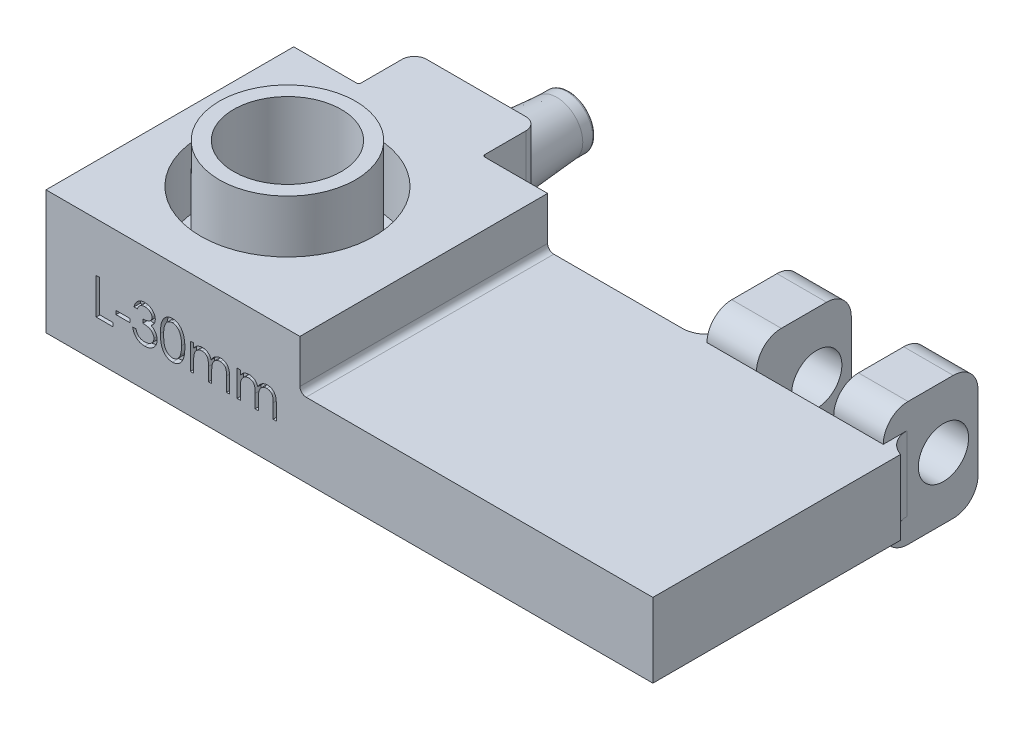
SolidWorks part; units mm, degrees
ref_plane "Front Plane" through (0, 0, 0) normal (0, 0, 1) x (1, 0, 0)
ref_plane "Top Plane" through (0, 0, 0) normal (0, 1, 0) x (1, 0, 0)
ref_plane "Right Plane" through (0, 0, 0) normal (1, 0, 0) x (0, 0, -1)
sketch "Sketch2" plane through (0, 0, 0) normal (0, 1, 0) x (1, 0, 0)
  line L1 (-14.4231, 13.5577) -> (34.5769, 13.5577)
  line L2 (-14.4231, 13.5577) -> (-14.4231, -6.4423)
  line L3 (-14.4231, -6.4423) -> (34.5769, -6.4423)
  line L4 (34.5769, 13.5577) -> (34.5769, -6.4423)
  dimension "D1" = 49
  dimension "D2" = 20
extrude "Boss-Extrude1" add sketch "Sketch2" along normal blind 10
sketch "Sketch3" plane through (0, 0, 0) normal (0, -1, 0) x (1, 0, 0)
  line L0 (34.5769, 6.4423) -> (34.5769, -13.5577) construction
  line L1 (27.5769, -5.0677) -> (-2.4231, -5.0677)
  line L2 (27.5769, -5.0677) -> (27.5769, -2.0477)
  line L3 (27.5769, -2.0477) -> (-2.4231, -2.0477)
  line L4 (-2.4231, -5.0677) -> (-2.4231, -2.0477)
  line L5 (-14.4231, -3.5577) -> (34.5769, -3.5577) construction
  line L6 (-14.4231, -13.5577) -> (-14.4231, 6.4423) construction
  dimension "D1" = 30
  dimension "D2" = 7
  dimension "D3" = 3.02
  dimension "D4" = 1.51
extrude "Cut-Extrude1" cut sketch "Sketch3" against normal blind 2
sketch "Sketch4" plane through (0, 0, 0) normal (0, -1, 0) x (1, 0, 0)
  line L0 (-2.4231, -2.0477) -> (-2.4231, -5.0677) construction
  line L1 (-2.4231, -6.0477) -> (-7.4231, -6.0477)
  line L2 (-2.4231, -6.0477) -> (-2.4231, -1.0477)
  line L3 (-2.4231, -1.0477) -> (-7.4231, -1.0477)
  line L4 (-7.4231, -6.0477) -> (-7.4231, -1.0477)
  line L6 (27.5769, -2.0477) -> (-2.4231, -2.0477) construction
  dimension "D1" = 5
  dimension "D2" = 5
  dimension "D3" = 1
extrude "Cut-Extrude2" cut sketch "Sketch4" against normal blind 5
sketch "Sketch5" plane through (0, 5, 0) normal (0, -1, 0) x (1, 0, 0)
  line L0 (-7.4231, -3.5477) -> (-2.4231, -3.5577) construction
  line L1 (-7.4231, -1.0477) -> (-7.4231, -6.0477) construction
  line L2 (-2.4231, -2.0477) -> (-2.4231, -5.0677) construction
  circle A0 centre (-4.9231, -3.5527) radius 7
  dimension "D1" = 14
extrude "Cut-Extrude3" cut sketch "Sketch5" against normal through all
sketch "Sketch6" plane through (0, 5, 0) normal (0, 1, 0) x (1, 0, 0)
  line L0 (-4.0731, 1.0477) -> (-2.4231, 1.0477)
  line L1 (-7.4231, 6.0477) -> (-5.7731, 6.0477)
  line L2 (-7.4231, 6.0477) -> (-7.4231, 1.0477)
  line L3 (-7.4231, 1.0477) -> (-5.7731, 1.0477)
  line L4 (-2.4231, 6.0477) -> (-2.4231, 1.0477)
  line L5 (-4.0731, 6.0477) -> (-2.4231, 6.0477)
  line L7 (-5.7731, 6.0477) -> (-5.7731, 1.0477)
  line L9 (-4.0731, 6.0477) -> (-4.0731, 1.0477)
  dimension "D1" = 1.7
extrude "Boss-Extrude2" add sketch "Sketch6" against normal blind 0.5
sketch "Sketch11" plane through (0, 0, 0) normal (0, -1, 0) x (1, 0, 0)
  circle A0 centre (28.8884, -3.5577) radius 2
  dimension "D1" = 4
extrude "Cut-Extrude4" cut sketch "Sketch11" against normal up to surface (2 mm away) up to face at (12.5769, 2, -3.5577)
sketch "Sketch12" plane through (0, 0, 0) normal (0, -1, 0) x (1, 0, 0)
  line L1 (-7.4231, -1.0477) -> (-2.4231, -1.0477)
  line L2 (-7.4231, -1.0477) -> (-7.4231, -6.0477)
  line L3 (-7.4231, -6.0477) -> (-2.4231, -6.0477)
  line L4 (-2.4231, -1.0477) -> (-2.4231, -6.0477)
extrude "Boss-Extrude4" add sketch "Sketch12" against normal blind 0.8
sketch "Sketch14" plane through (0, 0, 6.4423) normal (0, 0, 1) x (1, 0, 0)
  line L0 (-14.4231, 10) -> (34.5769, 10) construction
  line L1 (6.0769, 10) -> (34.5769, 10)
  line L2 (6.0769, 10) -> (6.0769, 6)
  line L3 (6.0769, 6) -> (34.5769, 6)
  line L4 (34.5769, 10) -> (34.5769, 6)
  line L5 (34.5769, 10) -> (34.5769, 0) construction
  line L6 (27.5769, 2) -> (-2.4231, 2) construction
  line L7 (2.0769, 5) -> (2.0769, 10) construction
  dimension "D1" = 4
  dimension "D2" = 4
extrude "Cut-Extrude6" cut sketch "Sketch14" against normal through all
fillet "Fillet1" radius 0.5 1 edges at (6.0769, 6, -3.5577)
sketch "Sketch13" plane through (0, 0, 6.4423) normal (0, 0, 1) x (1, 0, 0)
  line L0 (-10.748, 3.1258) -> (12.5164, 3.1258) construction
  text T0 "L-30mm" font "Century Gothic" height in points 11
extrude "Cut-Extrude5" cut sketch "Sketch13" against normal blind 0.5
sketch "Sketch19" plane through (0, 10, 0) normal (0, 1, 0) x (1, 0, 0)
  line L0 (6.0769, 13.5577) -> (-14.4231, 13.5577) construction
  line L1 (-9.1731, 18.0477) -> (0.8269, 18.0477)
  line L2 (-9.1731, 18.0477) -> (-9.1731, 13.5577)
  line L3 (-9.1731, 13.5577) -> (0.8269, 13.5577)
  line L4 (0.8269, 18.0477) -> (0.8269, 13.5577)
  line L6 (-4.1731, -6.4423) -> (-4.1731, 18.0477) construction
  line L8 (-14.4231, -6.4423) -> (6.0769, -6.4423) construction
  dimension "D1" = 10
  dimension "D3" = 12
extrude "Boss-Extrude5" add sketch "Sketch19" against normal up to surface (10 mm away) up to face at (13.4048, 0, -3.5577)
fillet "Fillet2" radius 1 2 edges at (-9.1731, 5, -18.0477) (0.8269, 5, -18.0477)
sketch "Sketch20" plane through (0, 0, -18.0477) normal (0, 0, -1) x (-1, 0, 0)
  line L0 (8.1731, 0) -> (0.1731, 0) construction
  circle A0 centre (4.6731, 3.5) radius 0.5
  dimension "D1" = 1
  dimension "D2" = 3.5
extrude "Cut-Extrude7" cut sketch "Sketch20" against normal up to next
sketch "Sketch21" plane through (0, 0, -18.0477) normal (0, 0, -1) x (-1, 0, 0)
  circle A0 centre (4.6731, 3.5) radius 1.4
  dimension "D1" = 2.8
extrude "Cut-Extrude8" cut sketch "Sketch21" against normal offset from surface (10 mm away) 2 up to face at (-5.1731, 3.5, -6.0477)
ref_axis "Axis1" through (-4.6731, 3.5, -8.0477) along (0, 0, -1)
ref_plane "Plane1" through (0, 3.5, 0) normal (0, -1, 0) x (-1, 0, 0)
sketch "Sketch23" plane through (0, 3.5, 0) normal (0, -1, 0) x (-1, 0, 0)
  line L0 (4.6731, 15.6131) -> (4.6731, 26.4829) construction
  line L1 (4.6731, 8.0477) -> (4.6731, 18.0477) construction
  line L2 (6.2731, 26.0477) -> (6.7731, 26.0477)
  line L3 (6.7731, 26.0477) -> (6.7731, 25.0477)
  line L4 (6.7731, 25.0477) -> (7.1731, 20.1558)
  line L5 (7.0734, 20.0477) -> (6.7731, 20.0477)
  line L6 (6.7731, 20.0477) -> (6.7731, 18.0477)
  line L7 (8.1731, 18.0477) -> (0.1731, 18.0477) construction
  line L8 (6.7731, 18.0477) -> (6.2731, 18.0477)
  line L9 (6.2731, 18.0477) -> (6.2731, 26.0477)
  arc A0 (7.0734, 20.0477) -> (7.1731, 20.1558) centre (7.0734, 20.1477) ccw
  dimension "D1" = 0.1
  dimension "D2" = 0.5
  dimension "D3" = 4.2
  dimension "D4" = 5
  dimension "D5" = 8
  dimension "D6" = 7
  dimension "D7" = 5
revolve "Revolve1" add sketch "Sketch23" angle 360 about L0
fillet "Fillet3" radius 0.2 5 edges at (-3.0731, 3.5, -26.0477) (-2.5731, 3.5, -26.0477) (-6.7731, 3.5, -18.0477)
sketch "Sketch24" plane through (0, 5, 0) normal (0, 1, 0) x (1, 0, 0)
  line L5 (-5.7731, 1.0477) -> (-5.7731, 6.0477) construction
  line L6 (-4.0731, 1.0477) -> (-5.7731, 1.0477)
  line L7 (-4.0731, 1.0477) -> (-4.0731, 4.0477)
  line L8 (-4.0731, 4.0477) -> (-5.7731, 4.0477)
  line L9 (-5.7731, 1.0477) -> (-5.7731, 4.0477)
  dimension "D1" = 3
extrude "Boss-Extrude6" add sketch "Sketch24" against normal up to vertex (0.5 mm away) up to point (-5.7731, 4.5, -1.0477)
sketch "Sketch29" plane through (0, 6, 0) normal (0, 1, 0) x (1, 0, 0)
  line L0 (29.0269, 13.5577) -> (29.0269, -8.2906) construction
  line L1 (34.5769, 13.5577) -> (34.5769, -6.4423) construction
  line L2 (23.0969, 13.5577) -> (23.0969, -8.2906) construction
  line L3 (34.5769, 13.5577) -> (1.0269, 13.5577) construction
  point P6 (0, 0)
  point P9 (0, 0)
  point P10 (0, 0)
  dimension "D1" = 5.55
  dimension "D2" = 5.93
sketch "Sketch34" plane through (0, 5, 0) normal (0, 1, 0) x (1, 0, 0)
  circle A0 centre (-4.9231, 3.5527) radius 4.35
  circle A1 centre (-4.9231, 3.5527) radius 5.5
  dimension "D1" = 8.7
  dimension "D2" = 11
extrude "Boss-Extrude10" add sketch "Sketch34" along normal blind 8.2
sketch "Sketch36" plane through (0, 0, -13.5577) normal (0, 0, -1) x (-1, 0, 0)
  line L0 (-6.5769, 6) -> (-34.5769, 6) construction
  line L1 (-34.5769, 3) -> (-17, 3) construction
  line L2 (-34.5769, 6) -> (-34.5769, 0) construction
  line L4 (-33.1769, -2) -> (-29.1769, -2)
  line L5 (-33.1769, -2) -> (-33.1769, 8)
  line L6 (-33.1769, 8) -> (-29.1769, 8)
  line L7 (-29.1769, -2) -> (-29.1769, 8)
  line L8 (-33.1769, -2) -> (-29.1769, 8) construction
  line L9 (-33.1769, 8) -> (-29.1769, -2) construction
  line L10 (-22.9469, -2) -> (-18.9469, -2)
  line L11 (-22.9469, -2) -> (-22.9469, 8)
  line L12 (-22.9469, 8) -> (-18.9469, 8)
  line L13 (-18.9469, -2) -> (-18.9469, 8)
  line L14 (-22.9469, -2) -> (-18.9469, 8) construction
  line L15 (-22.9469, 8) -> (-18.9469, -2) construction
  point P0 (-29.0269, 6)
  point P1 (-31.1769, 3)
  point P5 (-23.0969, 6)
  point P15 (-20.9469, 3)
  dimension "D1" = 10
  dimension "D2" = 4
  dimension "D3" = 0.15
  dimension "D4" = 0.15
extrude "Boss-Extrude11" add sketch "Sketch36" along normal blind 7.65
sketch "Sketch37" plane through (33.1769, 0, 0) normal (1, 0, 0) x (0, 0, -1)
  line L0 (21.2077, 8) -> (21.2077, -2) construction
  line L1 (13.5577, 6) -> (13.5577, 0) construction
  circle A0 centre (18.4177, 3) radius 2.03
  point P4 (0, 0)
  point P7 (13.5577, 3)
  dimension "D1" = 4.06
  dimension "D2" = 2.79
extrude "Cut-Extrude9" cut sketch "Sketch37" against normal up to surface (14.23 mm away) up to face at (18.9469, 3, -16.1077)
fillet "Fillet4" radius 2 10 edges at (20.9469, 8, -13.5577) (20.9469, 8, -21.2077) (31.1769, -2, -21.2077) (20.9469, -2, -21.2077) (20.9469, -2, -13.5577) (31.1769, -2, -13.5577) (31.1769, 8, -13.5577) (31.1769, 8, -21.2077) (18.9469, 3, -13.5577) (33.1769, 3, -13.5577)
